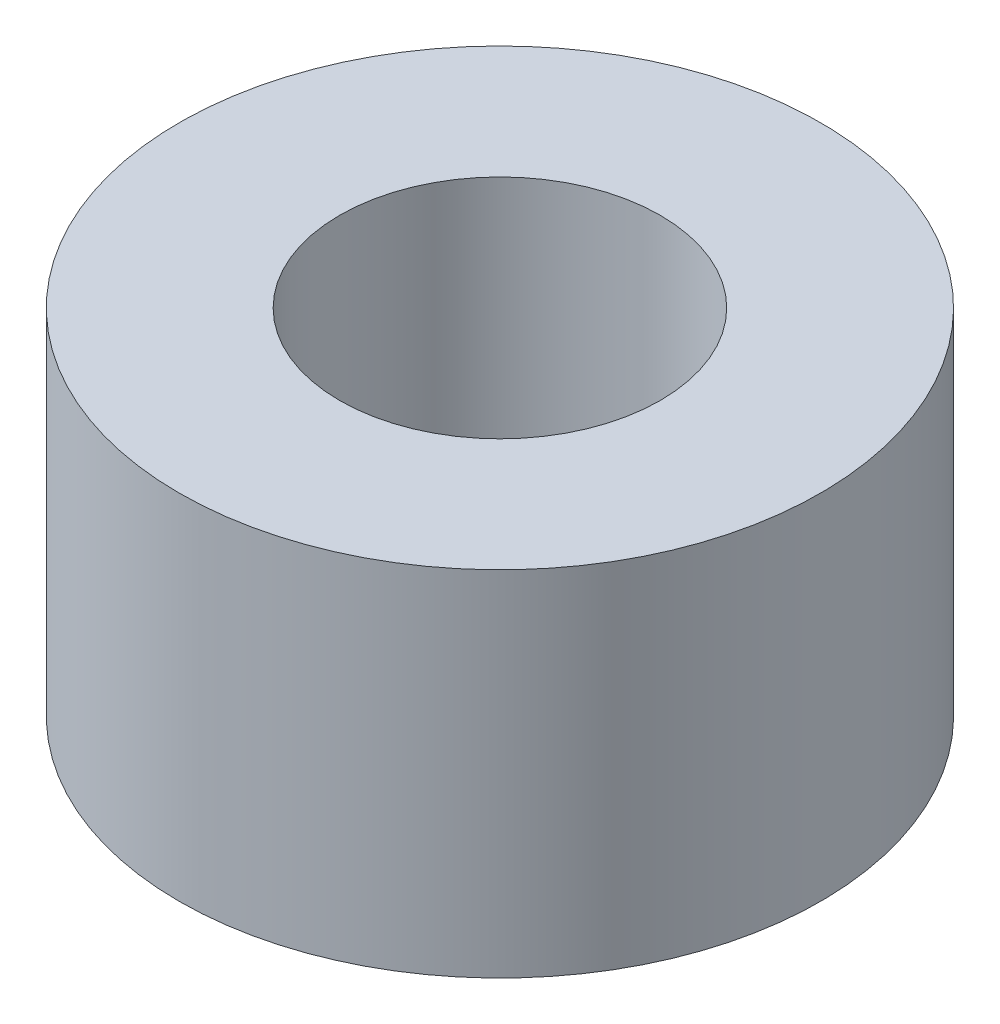
SolidWorks part; units mm, degrees
ref_plane "Front Plane" through (0, 0, 0) normal (0, 0, 1) x (1, 0, 0)
ref_plane "Top Plane" through (0, 0, 0) normal (0, 1, 0) x (1, 0, 0)
ref_plane "Right Plane" through (0, 0, 0) normal (1, 0, 0) x (0, 0, -1)
sketch "Sketch1" plane through (0, 0, 0) normal (0, 1, 0) x (1, 0, 0)
  circle A0 centre (0, 0) radius 6.35
  circle A1 centre (0, 0) radius 12.7
  dimension "D1" = 12.7
  dimension "D2" = 6.35
extrude "Boss-Extrude1" add sketch "Sketch1" along normal blind 14
